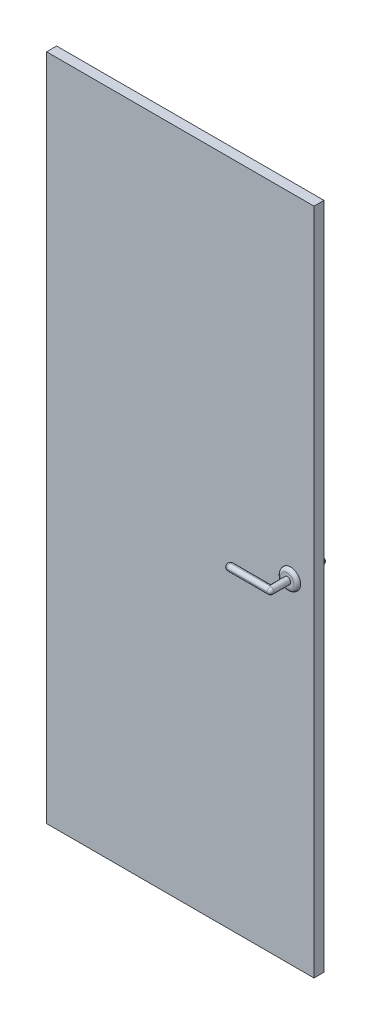
SolidWorks part; units mm, degrees
ref_plane "Спереди" through (0, 0, 0) normal (0, 0, 1) x (1, 0, 0)
ref_plane "Сверху" through (0, 0, 0) normal (0, 1, 0) x (1, 0, 0)
ref_plane "Справа" through (0, 0, 0) normal (1, 0, 0) x (0, 0, -1)
sketch "Эскиз1" plane through (46095.7396, 0, 0) normal (0, 0, -1) x (-1, 0, 0)
  line L1 (45295.7396, 2000) -> (46095.7396, 2000)
  line L2 (45295.7396, 2000) -> (45295.7396, 0)
  line L3 (45295.7396, 0) -> (46095.7396, 0)
  line L4 (46095.7396, 2000) -> (46095.7396, 0)
  dimension "D1" = 800
  dimension "D2" = 2000
extrude "Бобышка-Вытянуть1" add sketch "Эскиз1" against normal blind 30
sketch "Эскиз2" plane through (0, 0, 0) normal (0, 0, -1) x (-1, 0, 0)
  line L0 (0, 0) -> (0, 2000) construction
  line L1 (0, 1605) -> (-20, 1605)
  line L2 (0, 1605) -> (0, 1705)
  line L3 (0, 1705) -> (-20, 1705)
  line L4 (-20, 1605) -> (-20, 1705)
  line L8 (0, 2000) -> (-800, 2000) construction
  dimension "D1" = 20
  dimension "D2" = 100
  dimension "D3" = 295
extrude "Бобышка-Вытянуть2" add sketch "Эскиз2" along normal blind 50
sketch "Эскиз3" plane through (0, 1605, 0) normal (0, -1, 0) x (-1, 0, 0)
  line L0 (-20, 50) -> (-20, 0) construction
  line L1 (-20, 50) -> (0, 50) construction
  circle A0 centre (5, 30) radius 20
  dimension "D3" = 40
  dimension "D1" = 25
  dimension "D2" = 20
extrude "Бобышка-Вытянуть3" add sketch "Эскиз3" against normal blind 100
pattern_linear "Линейный массив1" count 2 spacing 1200 along (0, -1, 0) of "Бобышка-Вытянуть2", "Бобышка-Вытянуть3"
sketch "Эскиз4" plane through (0, 0, 0) normal (0, 0, -1) x (-1, 0, 0)
  line L0 (-800, 2000) -> (-800, 0) construction
  line L1 (-800, 0) -> (0, 0) construction
  circle A0 centre (-730, 1000) radius 30
  dimension "D1" = 60
  dimension "D2" = 70
  dimension "D3" = 1000
extrude "Бобышка-Вытянуть4" add sketch "Эскиз4" along normal blind 10
sketch "Эскиз5" plane through (0, 0, -10) normal (0, 0, -1) x (-1, 0, 0)
  circle A0 centre (-730, 1000) radius 10
  dimension "D1" = 20
extrude "Бобышка-Вытянуть5" add sketch "Эскиз5" along normal blind 40
sketch "Эскиз6" plane through (0, 0, -50) normal (0, 0, -1) x (-1, 0, 0)
  line L0 (-730, 1000) -> (-610, 1000) construction
  line L5 (-730, 1010) -> (-610, 1010)
  line L6 (-730, 990) -> (-610, 990)
  line L7 (-740, 1000) -> (-600, 1000) construction
  arc A1 (-730, 1010) -> (-730, 990) centre (-730, 1000) ccw
  arc A2 (-610, 990) -> (-610, 1010) centre (-610, 1000) ccw
  circle A3 centre (-730, 1000) radius 10 construction
  point P2 (-670, 1000)
  dimension "D1" = 140
extrude "Бобышка-Вытянуть6" add sketch "Эскиз6" along normal blind 20
fillet "Скругление1" radius 10 8 edges at (670, 1010, -50) (600, 1000, -50) (670, 1010, -70) (600, 1000, -70) (670, 990, -70) (740, 1000, -70) (700, 1000, -10) (670, 990, -50)
ref_plane "Плоскость1" through (0, 0, 15) normal (0, 0, -1) x (-1, 0, 0)
mirror "Зеркальное отражение1" about plane through (0, 0, 15) normal (0, 0, -1) of "Скругление1", "Бобышка-Вытянуть4", "Бобышка-Вытянуть5", "Бобышка-Вытянуть6"
